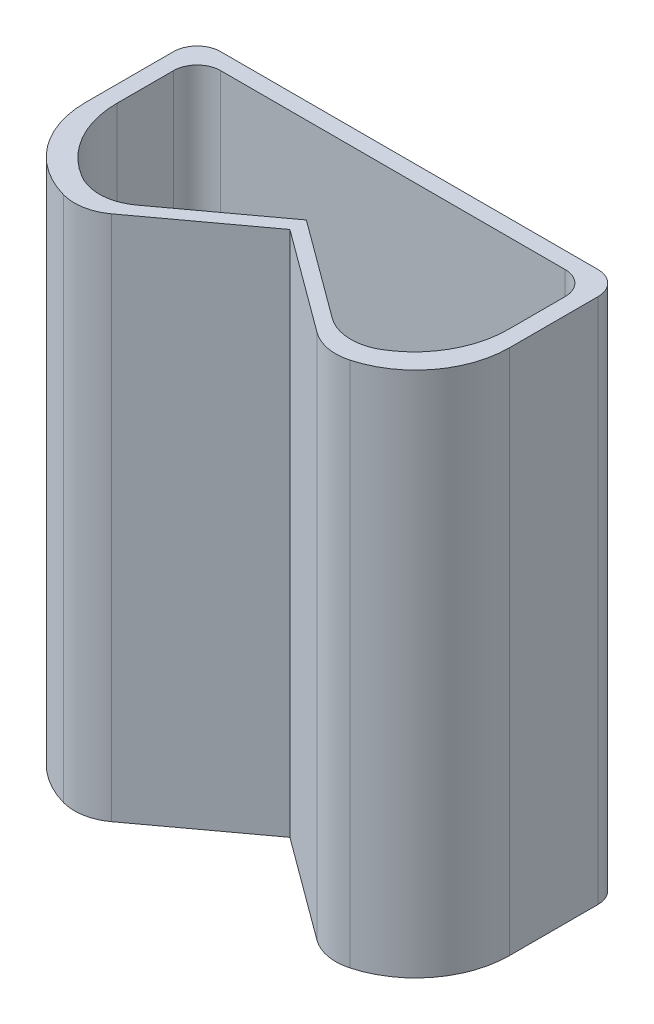
SolidWorks part; units mm, degrees
ref_plane "정면" through (0, 0, 0) normal (0, 0, 1) x (1, 0, 0)
ref_plane "윗면" through (0, 0, 0) normal (0, 1, 0) x (1, 0, 0)
ref_plane "우측면" through (0, 0, 0) normal (1, 0, 0) x (0, 0, -1)
sketch "스케치1" plane through (0, 0, 0) normal (0, 0, 1) x (1, 0, 0)
  line L1 (-4.515, -5.6) -> (4.515, -5.6)
  line L2 (-4.515, -5.6) -> (-4.515, 5.6)
  line L3 (-4.515, 5.6) -> (4.515, 5.6)
  line L4 (4.515, -5.6) -> (4.515, 5.6)
  line L5 (-4.515, -5.6) -> (4.515, 5.6) construction
  line L6 (-4.515, 5.6) -> (4.515, -5.6) construction
  point P0 (0, 0)
  dimension "D1" = 9.03
  dimension "D2" = 11.2
extrude "보스-돌출1" add sketch "스케치1" along normal blind 4.38
fillet "필렛1" radius 0.5 2 edges at (4.515, 0, 0) (-4.515, 0, 0)
sketch "스케치2" plane through (0, 5.6, 0) normal (0, 1, 0) x (1, 0, 0)
  line L0 (-3.9581, -0.35) -> (3.4451, -0.35) construction
  line L1 (4.015, 0) -> (-4.015, 0) construction
  line L2 (4.165, 0.722) -> (4.165, -4.4984) construction
  line L3 (4.515, -4.38) -> (4.515, -0.5) construction
  line L4 (-4.7829, -4.03) -> (5.6378, -4.03) construction
  line L5 (4.515, -4.38) -> (-4.515, -4.38) construction
  line L6 (-4.165, 0.9131) -> (-4.165, -4.9611) construction
  line L7 (-4.515, -4.38) -> (-4.515, -0.5) construction
  line L8 (4.165, -0.35) -> (4.165, -4.03)
  line L9 (4.165, -4.03) -> (-4.165, -4.03)
  line L10 (-4.165, -4.03) -> (-4.165, -0.35)
  line L11 (-4.165, -0.35) -> (4.165, -0.35)
  line L12 (0, -0.35) -> (0, -4.03) construction
  line L13 (-2.5, 1.2518) -> (-2.5, -5.5181) construction
  line L14 (2.5, 1.2518) -> (2.5, -5.5181) construction
  line L15 (-2.5, -4.03) -> (0, -2.19)
  line L16 (0, -2.19) -> (2.5, -4.03)
  line L17 (-2.5, -4.38) -> (0, -2.54)
  line L18 (4.515, -4.38) -> (-4.515, -4.38) construction
  line L19 (2.5, -4.38) -> (0, -2.54)
  line L20 (-2.5, -4.38) -> (2.5, -4.38)
  line M9 (-4.515, -4.38) -> (4.515, -4.38)
  dimension "D1" = 0.35
  dimension "D2" = 0.35
  dimension "D3" = 0.35
  dimension "D4" = 0.35
  dimension "D5" = 2.5
  dimension "D6" = 0
extrude "컷-돌출2" cut sketch "스케치2" against normal blind 14.38 contours L15 L16 L9 L8 L11 L10 | L19 L9 L17 M9 | L9 L19 L17 region at (0, 5.6, 1.9734) region at (0, 5.6, 4.2111) region at (0, 5.6, 3.5333)
fillet "필렛5" radius 2 4 edges at (4.165, 0, 4.03) (4.515, 0, 4.38) (-4.165, 0, 4.03) (-4.515, 0, 4.38)
fillet "필렛6" radius 1 4 edges at (2.5, 0, 4.03) (2.5, 0, 4.38) (-2.5, 0, 4.38) (-2.5, 0, 4.03)
fillet "필렛7" radius 0.5 2 edges at (4.165, 0, 0.35) (-4.165, 0, 0.35)
